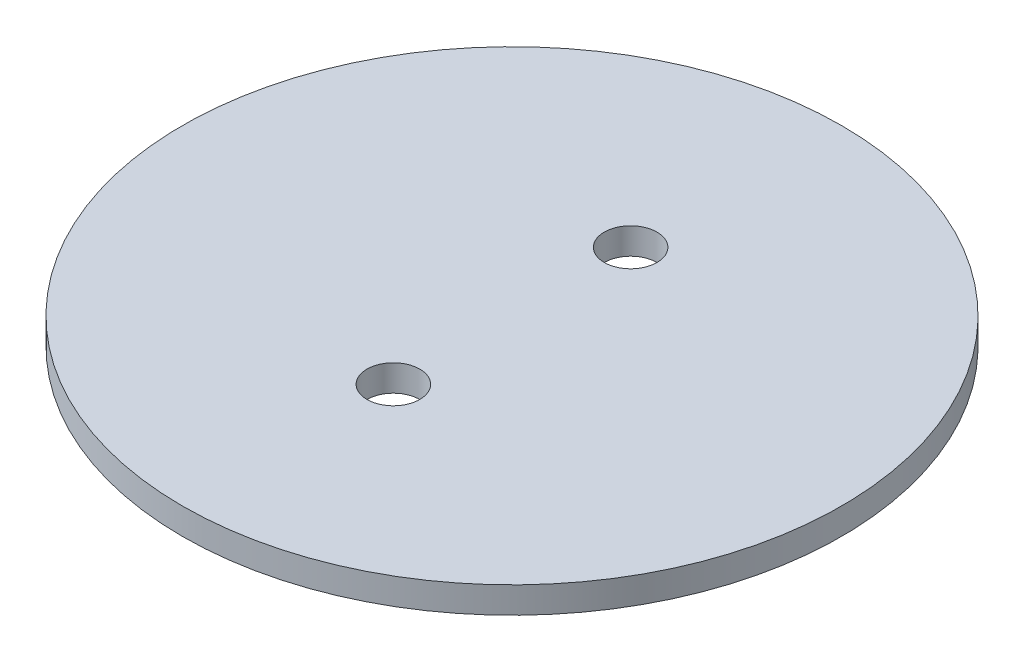
SolidWorks part; units mm, degrees
ref_plane "Front Plane" through (0, 0, 0) normal (0, 0, 1) x (1, 0, 0)
ref_plane "Top Plane" through (0, 0, 0) normal (0, 1, 0) x (1, 0, 0)
ref_plane "Right Plane" through (0, 0, 0) normal (1, 0, 0) x (0, 0, -1)
sketch "Sketch1" plane through (0, 0, 0) normal (0, 1, 0) x (1, 0, 0)
  line L0 (-28.5, 0) -> (28.5, 0) construction
  line L1 (0, 0) -> (0, 13.5)
  line L2 (0, 0) -> (0, -13.5)
  circle A0 centre (0, 0) radius 37.5
  circle A1 centre (28.5, 0) radius 3 construction
  circle A2 centre (-28.5, 0) radius 3 construction
  circle A3 centre (0, 13.5) radius 3
  circle A4 centre (0, -13.5) radius 3
  circle A5 centre (-28.5, 0) radius 6.25 construction
  circle A6 centre (0, 13.5) radius 12.5 construction
  circle A7 centre (0, -13.5) radius 12.5 construction
  circle A8 centre (28.5, 0) radius 6.25 construction
  point P11 (0, 0)
  dimension "D1" = 75
  dimension "D3" = 6
  dimension "D4" = 13.5
  dimension "D5" = 6
  dimension "D6" = 12.5
  dimension "D7" = 25
  dimension "D2" = 57
extrude "Boss-Extrude1" add sketch "Sketch1" against normal blind 3 contours A0 A4 A3 A2 A1 region at (-36.4393, 0, 0)
